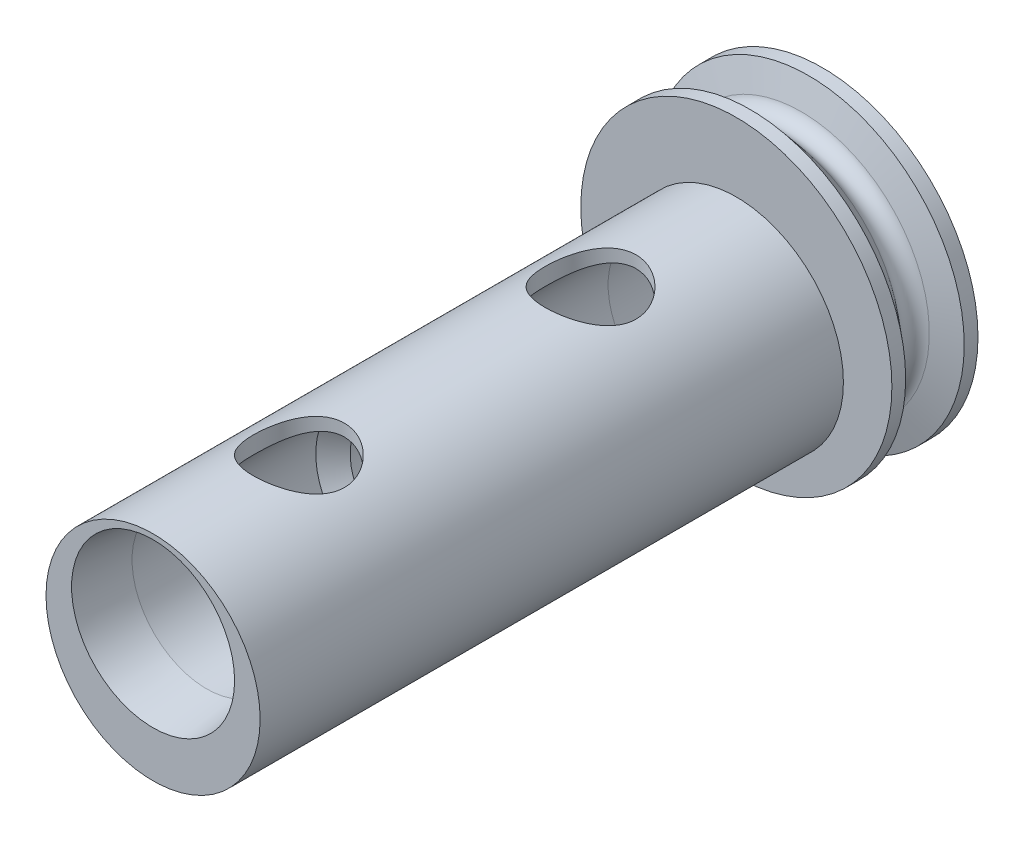
SolidWorks part; units mm, degrees
material "ABS"
ref_plane "Front Plane" through (0, 0, 0) normal (0, 0, 1) x (1, 0, 0)
ref_plane "Top Plane" through (0, 0, 0) normal (0, 1, 0) x (1, 0, 0)
ref_plane "Right Plane" through (0, 0, 0) normal (1, 0, 0) x (0, 0, -1)
sketch "Sketch1" plane through (0, 0, 0) normal (0, 0, 1) x (1, 0, 0)
  circle A1 centre (0, 0) radius 9.525 construction
  circle A2 centre (0, 0) radius 9.525 construction
  circle A3 centre (0, 0) radius 9.325
  dimension "D3" = 0.2
extrude "Boss-Extrude1" add sketch "Sketch1" against normal up to surface (50.8 mm away)
sketch "Sketch2" plane through (0, 0, 0) normal (0, 1, 0) x (1, 0, 0)
  circle A0 centre (0, 38.1) radius 3.9688
  circle A1 centre (0, 12.7) radius 3.9688
  dimension "D1" = 7.9375
extrude "Cut-Extrude1" cut sketch "Sketch2" along normal blind 10.16 from offset 1.27
ref_axis "Axis1" through (0, 1.778, -24.4249) along (0, 0, 1)
sketch "Sketch3" plane through (0, 0, 0) normal (1, 0, 0) x (0, 0, -1)
  line L0 (50.8, 1.778) -> (50.8, 15.325)
  line L1 (50.8, 15.325) -> (52, 15.325)
  line L2 (52, 15.325) -> (54.3954, 12.4702)
  line L3 (56.4576, 12.9274) -> (57.1, 15.325)
  line L4 (57.1, 15.325) -> (58.3, 15.325)
  line L5 (58.3, 15.325) -> (58.3, 1.778)
  line L6 (58.3, 1.778) -> (50.8, 1.778)
  line L7 (50.8, -9.325) -> (50.8, 9.325) construction
  line L8 (24.4249, 1.778) -> (-26.3751, 1.778) construction
  line L9 (50.8, 9.325) -> (42.0688, 9.325) construction
  arc A0 (54.3954, 12.4702) -> (56.4576, 12.9274) centre (55.3075, 13.2355) ccw
  point P16 (46.4344, 9.325)
  dimension "D1" = 50
  dimension "D3" = 1.1906
  dimension "D2" = 1.2
  dimension "D4" = 6
  dimension "D5" = 75
  dimension "D6" = 7.5
revolve "Revolve1" add sketch "Sketch3" angle 360 about axis through (0, 1.778, -24.4249) along (0, 0, 1)
sketch "Sketch4" plane through (0, 0, 0) normal (0, 0, 1) x (1, 0, 0)
  point P0 (0, 1.775)
  dimension "D1" = 1.775
sketch "Sketch5" plane through (0, 0, 0) normal (1, 0, 0) x (0, 0, -1)
  line L0 (0, 1.778) -> (58.3, 1.778)
  line L3 (24.4249, 1.778) -> (-26.3751, 1.778) construction
  line L4 (0, 9.325) -> (0, -9.325) construction
  line L5 (58.3, -11.769) -> (58.3, 15.325) construction
  line L6 (4.6687, 8.278) -> (20.6687, 8.278)
  line L7 (30.1313, 8.278) -> (46.1313, 8.278)
  line L8 (20.6687, 8.278) -> (22.1687, 6.778)
  line L9 (22.1687, 6.778) -> (28.6313, 6.778)
  line L10 (28.6313, 6.778) -> (30.1313, 8.278)
  line L11 (34.1313, 9.325) -> (16.6687, 9.325) construction
  line L12 (4.6687, 8.278) -> (0, 8.878)
  line L13 (46.1313, 8.278) -> (58.3, 8.878)
  line L14 (0, 8.878) -> (0, 1.778)
  line L15 (58.3, 8.878) -> (58.3, 1.778)
  spline S0 degree 2 poles (16.6687, 9.325) (12.7, 7.6359) (8.7312, 9.325) knots 0 0 0 1 1 1 weights 0.005356 0.009325 0.013294 construction
  point P13 (25.4, 9.325)
  point P16 (25.4, 6.778)
  point P25 (16.6687, 9.325)
  dimension "D1" = 16
  dimension "D2" = 45
  dimension "D3" = 6.5
  dimension "D4" = 0.6
  dimension "D5" = 4
  dimension "D6" = 5
revolve "Cut-Revolve1" cut sketch "Sketch5" angle 360 about L0
ref_plane "Plane1" through (0, 0, -29.15) normal (0, 0, 1) x (1, 0, 0)
